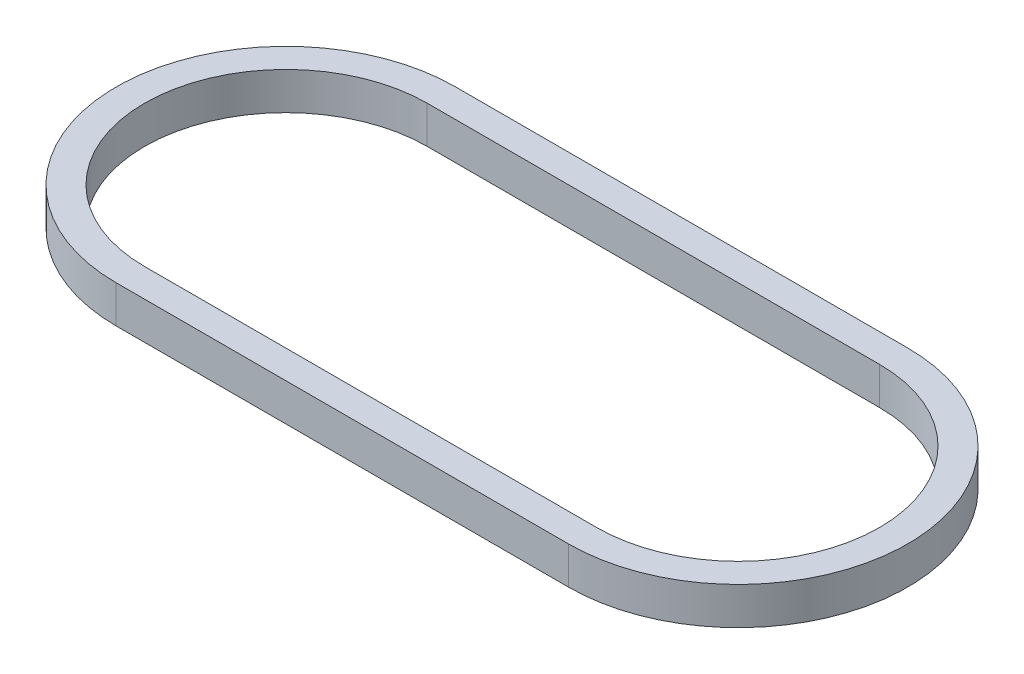
SolidWorks part; units mm, degrees
material "6061 Alloy"
ref_plane "Front Plane" through (0, 0, 0) normal (0, 0, 1) x (1, 0, 0)
ref_plane "Top Plane" through (0, 0, 0) normal (0, 1, 0) x (1, 0, 0)
ref_plane "Right Plane" through (0, 0, 0) normal (1, 0, 0) x (0, 0, -1)
sketch "Sketch1" plane through (0, 0, 0) normal (0, 1, 0) x (1, 0, 0)
  line L0 (-47.1, 0) -> (47.1, 0) construction
  line L1 (-47.1, 0) -> (47.1, 0) construction
  line L2 (-47.1, 35.3387) -> (47.1, 35.3387)
  line L3 (-47.1, -35.3387) -> (47.1, -35.3387)
  line L4 (-47.1, 0) -> (47.1, 0) construction
  line L5 (-47.1, 29.4459) -> (47.1, 29.4459)
  line L6 (-47.1, -29.4459) -> (47.1, -29.4459)
  line L7 (-47.1, 29.4459) -> (-47.1, 35.3387) construction
  arc A0 (-47.1, 35.3387) -> (-47.1, -35.3387) centre (-47.1, 0) ccw
  arc A1 (47.1, -35.3387) -> (47.1, 35.3387) centre (47.1, 0) ccw
  arc A2 (-47.1, 29.4459) -> (-47.1, -29.4459) centre (-47.1, 0) ccw
  arc A3 (47.1, -29.4459) -> (47.1, 29.4459) centre (47.1, 0) ccw
  point P0 (0, 0)
  point P4 (0, 0)
  point P10 (0, 0)
  point P18 (-47.1, 32.3923)
  dimension "D2" = 32.3923
  dimension "D3" = 5.8928
  dimension "D1" = 94.2
extrude "Boss-Extrude1" add sketch "Sketch1" along normal blind 7.7978 contours L3 A1 L2 A0 | L6 A2 L5 A3
